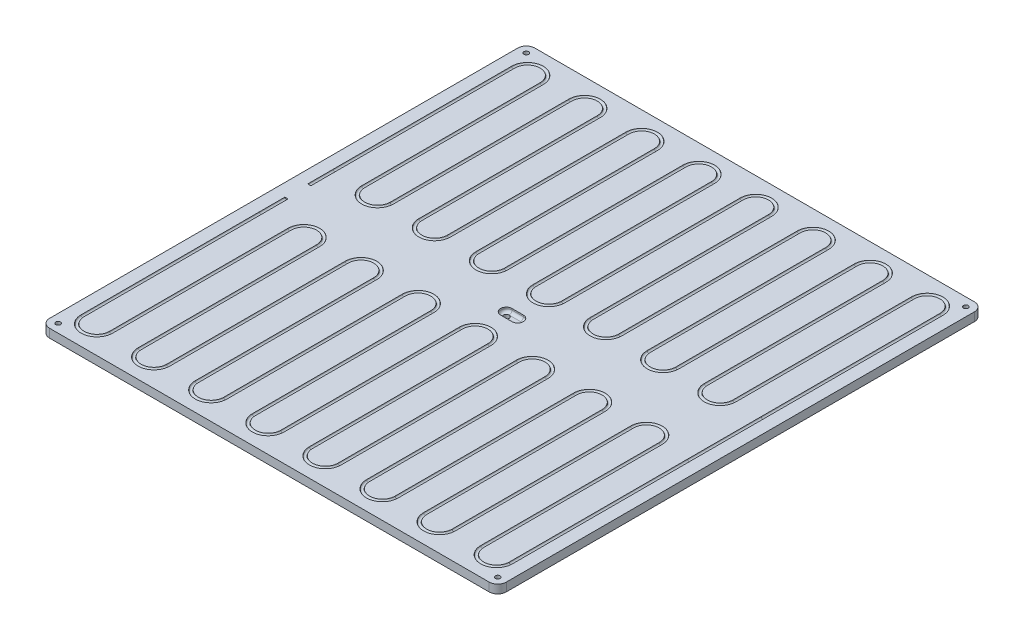
SolidWorks part; units mm, degrees
material "Клен"
ref_plane "Спереди" through (0, 0, 0) normal (0, 0, 1) x (1, 0, 0)
ref_plane "Сверху" through (0, 0, 0) normal (0, 1, 0) x (1, 0, 0)
ref_plane "Справа" through (0, 0, 0) normal (1, 0, 0) x (0, 0, -1)
sketch "Эскиз1" plane through (0, 0, 0) normal (0, 1, 0) x (1, 0, 0)
  line L0 (-199.4521, 0) -> (246.9406, 0) construction
  line L1 (-154, -156) -> (154, -156)
  line L2 (-160, -150) -> (-160, 178)
  line L3 (-154, 184) -> (154, 184)
  line L4 (160, -150) -> (160, 178)
  line L5 (-160, -160) -> (160, 160) construction
  line L6 (-160, 160) -> (160, -160) construction
  line L7 (0, -194.3379) -> (0, 187.7626) construction
  arc A0 (-154, -156) -> (-160, -150) centre (-154, -150) cw
  arc A1 (154, -156) -> (160, -150) centre (154, -150) ccw
  arc A2 (154, 184) -> (160, 178) centre (154, 178) cw
  arc A3 (-160, 178) -> (-154, 184) centre (-154, 178) cw
  point P0 (0, 0)
  dimension "D2" = 6
  dimension "D1" = 320
  dimension "D3" = 340
extrude "Бобышка-Вытянуть1" add sketch "Эскиз1" along normal blind 6
ref_plane "widht" through (0, 0, 0) normal (-1, 0, 0) x (0, 0, 1)
ref_plane "Плоскость2" through (0, 0, -14) normal (0, 0, -1) x (-1, 0, 0)
sketch "Эскиз2" plane through (0, 6, 0) normal (0, 1, 0) x (1, 0, 0)
  line L0 (-150, 39.8235) -> (-150, 164.8235)
  line L1 (-130, 39.8235) -> (-130, 164.8235)
  line L4 (-160, 178) -> (-160, -150) construction
  line L5 (-110, 39.8235) -> (-110, 164.8235)
  line L6 (-90, 39.8235) -> (-90, 164.8235)
  line L7 (-70, 39.8235) -> (-70, 164.8235)
  line L8 (-50, 39.8235) -> (-50, 164.8235)
  line L9 (-30, 39.8235) -> (-30, 164.8235)
  line L10 (-10, 39.8235) -> (-10, 164.8235)
  line L11 (10, 39.8235) -> (10, 164.8235)
  line L12 (30, 39.8235) -> (30, 164.8235)
  line L13 (50, 39.8235) -> (50, 164.8235)
  line L14 (70, 39.8235) -> (70, 164.8235)
  line L15 (90, 39.8235) -> (90, 164.8235)
  line L16 (110, 39.8235) -> (110, 164.8235)
  line L17 (130, 39.8235) -> (130, 164.8235)
  line L18 (150, 39.8235) -> (150, 164.8235)
  line L21 (3.3, 14) -> (-3.3, 14) construction
  line L22 (-150, 22) -> (-150, 39.8235)
  line L23 (-150, 6) -> (-150, -11.8235)
  line L24 (150, -11.8235) -> (150, -136.8235)
  line L25 (130, -11.8235) -> (130, -136.8235)
  line L26 (110, -11.8235) -> (110, -136.8235)
  line L27 (90, -11.8235) -> (90, -136.8235)
  line L28 (70, -11.8235) -> (70, -136.8235)
  line L29 (50, -11.8235) -> (50, -136.8235)
  line L30 (30, -11.8235) -> (30, -136.8235)
  line L31 (10, -11.8235) -> (10, -136.8235)
  line L32 (-10, -11.8235) -> (-10, -136.8235)
  line L33 (-30, -11.8235) -> (-30, -136.8235)
  line L34 (-50, -11.8235) -> (-50, -136.8235)
  line L35 (-70, -11.8235) -> (-70, -136.8235)
  line L36 (-90, -11.8235) -> (-90, -136.8235)
  line L37 (-110, -11.8235) -> (-110, -136.8235)
  line L38 (-130, -11.8235) -> (-130, -136.8235)
  line L39 (-150, -11.8235) -> (-150, -136.8235)
  line L40 (150, -11.8235) -> (150, 39.8235)
  line L41 (-205.3814, 22) -> (201.4691, 22) construction
  arc A0 (-150, 164.8235) -> (-130, 164.8235) centre (-140, 164.8235) cw
  arc A1 (-110, 164.8235) -> (-90, 164.8235) centre (-100, 164.8235) cw
  arc A2 (-70, 164.8235) -> (-50, 164.8235) centre (-60, 164.8235) cw
  arc A3 (-30, 164.8235) -> (-10, 164.8235) centre (-20, 164.8235) cw
  arc A4 (10, 164.8235) -> (30, 164.8235) centre (20, 164.8235) cw
  arc A5 (50, 164.8235) -> (70, 164.8235) centre (60, 164.8235) cw
  arc A6 (90, 164.8235) -> (110, 164.8235) centre (100, 164.8235) cw
  arc A7 (130, 164.8235) -> (150, 164.8235) centre (140, 164.8235) cw
  arc A8 (-130, 39.8235) -> (-110, 39.8235) centre (-120, 39.8235) ccw
  arc A9 (-90, 39.8235) -> (-70, 39.8235) centre (-80, 39.8235) ccw
  arc A10 (-50, 39.8235) -> (-30, 39.8235) centre (-40, 39.8235) ccw
  arc A11 (-10, 39.8235) -> (10, 39.8235) centre (0, 39.8235) ccw
  arc A12 (30, 39.8235) -> (50, 39.8235) centre (40, 39.8235) ccw
  arc A13 (70, 39.8235) -> (90, 39.8235) centre (80, 39.8235) ccw
  arc A14 (110, 39.8235) -> (130, 39.8235) centre (120, 39.8235) ccw
  arc A15 (110, -11.8235) -> (130, -11.8235) centre (120, -11.8235) cw
  arc A16 (70, -11.8235) -> (90, -11.8235) centre (80, -11.8235) cw
  arc A17 (30, -11.8235) -> (50, -11.8235) centre (40, -11.8235) cw
  arc A18 (-10, -11.8235) -> (10, -11.8235) centre (0, -11.8235) cw
  arc A19 (-50, -11.8235) -> (-30, -11.8235) centre (-40, -11.8235) cw
  arc A20 (-90, -11.8235) -> (-70, -11.8235) centre (-80, -11.8235) cw
  arc A21 (-130, -11.8235) -> (-110, -11.8235) centre (-120, -11.8235) cw
  arc A22 (130, -136.8235) -> (150, -136.8235) centre (140, -136.8235) ccw
  arc A23 (90, -136.8235) -> (110, -136.8235) centre (100, -136.8235) ccw
  arc A24 (50, -136.8235) -> (70, -136.8235) centre (60, -136.8235) ccw
  arc A25 (10, -136.8235) -> (30, -136.8235) centre (20, -136.8235) ccw
  arc A26 (-30, -136.8235) -> (-10, -136.8235) centre (-20, -136.8235) ccw
  arc A27 (-70, -136.8235) -> (-50, -136.8235) centre (-60, -136.8235) ccw
  arc A28 (-110, -136.8235) -> (-90, -136.8235) centre (-100, -136.8235) ccw
  arc A29 (-150, -136.8235) -> (-130, -136.8235) centre (-140, -136.8235) ccw
  point P0 (-150, 22)
  point P105 (-420.7427, 88.0821)
  dimension "D1" = 125
  dimension "D4" = 8
  dimension "D2" = 20
  dimension "D5" = 10
  dimension "D6" = 8
ref_plane "Плоскость3" through (0, 0, -22) normal (0, 0, 1) x (1, 0, 0)
sketch "Эскиз3" plane through (0, 0, -22) normal (0, 0, 1) x (1, 0, 0)
  circle A1 centre (-150, 6) radius 1.1
  dimension "D1" = 2.2
sketch "Эскиз4" plane through (0, 6, 0) normal (0, 1, 0) x (1, 0, 0)
  line L0 (-4, 14) -> (4, 14) construction
  line L1 (3.3, 14) -> (-3.3, 14) construction
  line L2 (0, 3.3) -> (0, -3.3) construction
  line L3 (-4, 18) -> (4, 18)
  line L4 (-4, 10) -> (4, 10)
  arc A0 (-4, 18) -> (-4, 10) centre (-4, 14) ccw
  arc A1 (4, 10) -> (4, 18) centre (4, 14) ccw
  point P6 (0, 14)
  dimension "D1" = 8
  dimension "D2" = 8
extrude "Вырез-Вытянуть1" cut sketch "Эскиз4" against normal blind 3
fillet "Скругление4" radius 2 4 edges at (0, 3, -18) (8, 3, -14) (0, 3, -10) (-8, 3, -14)
sweep "Вырез-По траектории1" cut profiles "Эскиз3" path "Эскиз2"
sketch "Эскиз5" plane through (0, 6, 0) normal (0, 1, 0) x (1, 0, 0)
  line L0 (0, 3.3) -> (0, -3.3) construction
  line L1 (3.3, 14) -> (-3.3, 14) construction
  circle A0 centre (-154, 178) radius 1.65
  circle A1 centre (154, 178) radius 1.65
  circle A2 centre (154, -150) radius 1.65
  circle A3 centre (-154, -150) radius 1.65
  circle A5 centre (-4, 14) radius 2
  point P0 (-154, 178)
  point P14 (-4, 14)
  dimension "D1" = 3.3
  dimension "D2" = 4
extrude "Вырез-Вытянуть2" cut sketch "Эскиз5" against normal through all
